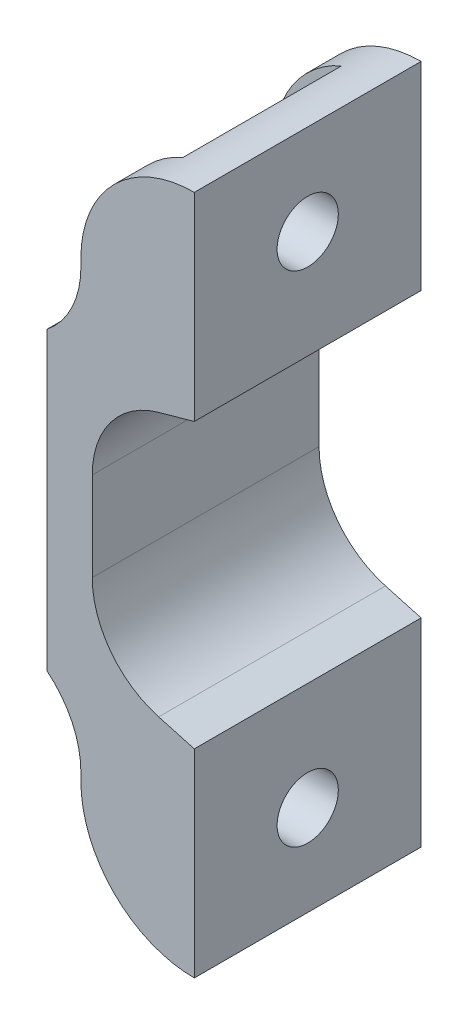
SolidWorks part; units mm, degrees
ref_plane "前视基准面" through (0, 0, 0) normal (0, 0, 1) x (1, 0, 0)
ref_plane "上视基准面" through (0, 0, 0) normal (0, 1, 0) x (1, 0, 0)
ref_plane "右视基准面" through (0, 0, 0) normal (1, 0, 0) x (0, 0, -1)
sketch "草图1" plane through (0, 0, 0) normal (0, 0, 1) x (1, 0, 0)
  line L0 (-478.9156, 0) -> (23466.8655, 0) construction
  line L1 (0, 30) -> (0, 12.5)
  line L2 (0, 12.5) -> (-9, 10)
  line L3 (-9, 10) -> (-9, -10)
  line L4 (-13, -13.0403) -> (-13, 13.0403)
  line L5 (-13, 13.0403) -> (-4, 15.5403)
  line L6 (-4, 15.5403) -> (-4, 30)
  line L7 (-4, 30) -> (0, 30)
  line L8 (-4, -30) -> (0, -30)
  line L9 (-4, -15.5403) -> (-4, -30)
  line L10 (-13, -13.0403) -> (-4, -15.5403)
  line L11 (0, -12.5) -> (-9, -10)
  line L12 (0, -30) -> (0, -12.5)
  point P15 (-13, 0)
  point P16 (-9, 0)
  dimension "D1" = 60
  dimension "D2" = 4
  dimension "D3" = 4
  dimension "D4" = 9
  dimension "D5" = 4
  dimension "D6" = 25
  dimension "D7" = 20
extrude "凸台-拉伸1" add sketch "草图1" along normal blind 10 and the other way blind 10
sketch "草图2" plane through (0, 0, 0) normal (1, 0, 0) x (0, 0, -1)
  line L0 (0, -22) -> (0, 22) construction
  circle A0 centre (0, 22) radius 2.7
  circle A1 centre (0, -22) radius 2.7
  point P4 (0, 0)
  dimension "D1" = 5.4
  dimension "D2" = 44
extrude "切除-拉伸1" cut sketch "草图2" against normal through all
sketch "草图3" plane through (0, 0, 0) normal (1, 0, 0) x (0, 0, -1)
  line L0 (10, 12.5) -> (-10, 12.5) construction
  line L1 (-10, 30) -> (-7, 30)
  line L2 (-10, 30) -> (-10, 12.5)
  line L3 (-10, 12.5) -> (-7, 12.5)
  line L4 (-7, 30) -> (-7, 12.5)
  line L5 (10, -12.5) -> (-10, -12.5) construction
  line L6 (10, 30) -> (7, 30)
  line L7 (10, 30) -> (10, 12.5)
  line L8 (10, 12.5) -> (7, 12.5)
  line L9 (7, 30) -> (7, 12.5)
  line L10 (-10, -30) -> (-7, -30)
  line L11 (-10, -30) -> (-10, -12.5)
  line L12 (-10, -12.5) -> (-7, -12.5)
  line L13 (-7, -30) -> (-7, -12.5)
  line L15 (10, -30) -> (7, -30)
  line L16 (10, -30) -> (10, -12.5)
  line L17 (10, -12.5) -> (7, -12.5)
  line L18 (7, -30) -> (7, -12.5)
  dimension "D1" = 3
extrude "凸台-拉伸2" add sketch "草图3" against normal blind 10
fillet "圆角1" radius 10 2 edges at (-10, -30, -8.5) (-10, 30, -8.5)
fillet "圆角2" radius 8 4 edges at (-10, 13.8737, 8.5) (-10, 13.8737, -8.5) (-10, -13.8737, 8.5) (-10, -13.8737, -8.5)
fillet "圆角3" radius 8 2 edges at (-9, 10, 0) (-9, -10, 0)
fillet "圆角4" radius 2 2 edges at (-4, 15.5403, 0) (-4, -15.5403, 0)
